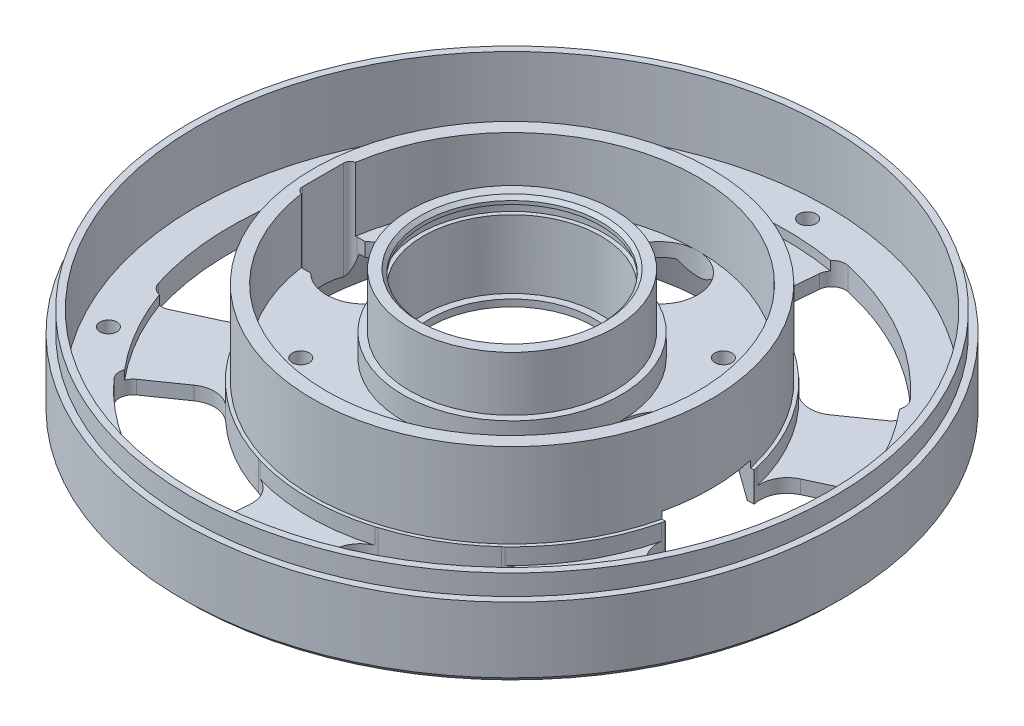
SolidWorks part; units mm, degrees
material "5052-H32"
ref_plane "Front Plane" through (0, 0, 0) normal (0, 0, 1) x (1, 0, 0)
ref_plane "Top Plane" through (0, 0, 0) normal (0, 1, 0) x (1, 0, 0)
ref_plane "Right Plane" through (0, 0, 0) normal (1, 0, 0) x (0, 0, -1)
ref_axis "Axis1" through (0, 0, 0) along (0, 1, 0)
sketch "Sketch1" plane through (0, 0, 0) normal (0, 0, 1) x (1, 0, 0)
  line L0 (0, 0) -> (0, -50000) construction
  line L1 (-13, 8.15) -> (-13, -4.15)
  line L2 (-13, -4.15) -> (-12, -4.15)
  line L4 (45.1, 8.15) -> (-45.1, 8.15) construction
  line L5 (-12.75, -4.15) -> (12.75, -4.15) construction
  line L7 (-13, 8.15) -> (-15, 8.15)
  line L8 (-15, 8.15) -> (-15, -3.15)
  line L9 (-15, -3.15) -> (-28.25, -3.15)
  line L10 (-12, -5.15) -> (-28.25, -5.15)
  line L12 (-28.25, -5.15) -> (-28.25, -3.15)
  line L13 (-29.25, 6) -> (-29.25, -6) construction
  line L16 (-12, -4.15) -> (-12, -5.15)
  dimension "D1" = 1
  dimension "D2" = 30
  dimension "D3" = 2
  dimension "D4" = 1
  dimension "D5" = 1
  dimension "D6" = 26
revolve "Revolve1" add sketch "Sketch1" angle 360 about L0
sketch "Sketch4" plane through (0, 0, 0) normal (0, 0, 1) x (1, 0, 0)
  line L1 (-29.75, -8.5) -> (-40.35, -8.5)
  line L2 (-46.35, -7.15) -> (-46.35, 3)
  line L3 (-46.35, 3) -> (-47.35, 3)
  line L4 (-47.35, 3) -> (-47.35, 0)
  line L5 (-47.35, 0) -> (-48.35, 0)
  line L6 (-48.35, 0) -> (-48.35, -9.6235)
  line L7 (-47.4735, -10.5) -> (-28.75, -10.5)
  line L8 (-28.75, -10.5) -> (-26.75, -5.15)
  line L9 (-29.75, -8.5) -> (-29.75, -6.1361)
  line L10 (-26.75, -5.15) -> (-26.75, -3.15)
  line L12 (-48.35, -9.6235) -> (-47.4735, -10.5)
  line L13 (-45.1, 8.15) -> (-45.1, -6.15) construction
  line L14 (-46.35, -7.15) -> (-40.35, -7.15)
  line L15 (-40.35, -7.15) -> (-40.35, -8.5)
  line L16 (-45.1, -6.15) -> (45.1, -6.15) construction
  line L18 (-44.85, -7.15) -> (-44.85, -10.5) construction
  line L20 (-41.85, -7.15) -> (-41.85, -10.5) construction
  line L22 (-29.75, -6.1361) -> (-29.23, -6.1361)
  line L24 (-29.23, -6.1361) -> (-29.23, -3.15)
  line L25 (-29.23, -3.15) -> (-26.75, -3.15)
  line L26 (28.25, -3.15) -> (-28.25, -3.15) construction
  line L27 (-39.5, -7.5) -> (39.5, -7.5) construction
  line L28 (0, 0) -> (0, 50000) construction
  line L29 (-30.25, -6) -> (-30.25, -7.5) construction
  line L33 (-28.25, -5.15) -> (28.25, -5.15) construction
  dimension "D1" = 2
  dimension "D2" = 3
  dimension "D3" = 1
  dimension "D4" = 2
  dimension "D5" = 0.5
  dimension "D6" = 1
  dimension "D7" = 1.25
  dimension "D8" = 135
  dimension "D9" = 3
  dimension "D10" = 1.5
  dimension "D11" = 1.5
  dimension "D12" = 2
  dimension "D13" = 1
  dimension "D14" = 58.46
revolve "Revolve2" add sketch "Sketch4" angle 360 about axis through (0, 0, 0) along (0, 1, 0)
sketch "Sketch6" plane through (0, 0, 0) normal (0, 0, 1) x (1, 0, 0)
  line L0 (-29.23, 6.233) -> (-27.23, 6.233)
  line L1 (-27.23, 6.233) -> (-27.23, -3.15)
  line L2 (-27.23, -3.15) -> (-29.23, -3.15)
  line L3 (-29.23, -3.15) -> (-29.23, 6.233)
  line L6 (29.23, -3.15) -> (-29.23, -3.15) construction
  dimension "D1" = 2
revolve "Revolve3" add sketch "Sketch6" angle 360 about axis through (0, 0, 0) along (0, 1, 0)
sketch "Sketch7" plane through (0, 0, 0) normal (0, 0, 1) x (1, 0, 0)
  line L0 (40.35, -8.5) -> (-40.35, -8.5) construction
  line L1 (-29.7176, -6.1376) -> (-29.23, -6.1376)
  line L2 (-29.73, -6.15) -> (-29.73, -8.5)
  line L3 (-29.73, -8.5) -> (-29.23, -8.5)
  line L4 (-29.23, -6.1376) -> (-29.23, -8.5)
  line L5 (-29.23, 6.233) -> (-29.23, -6.1361) construction
  line L6 (-29.7176, -6.1376) -> (-29.73, -6.15)
  line L7 (29.75, -8.5) -> (-29.75, -8.5) construction
  line L8 (-31.759, -6.15) -> (-25.7399, -6.15) construction
  dimension "D1" = 135
  dimension "D2" = 0.5
revolve "Revolve4" add sketch "Sketch7" angle 360 about axis through (0, 0, 0) along (0, 1, 0)
sketch "Sketch8" plane through (0, -5.15, 0) normal (0, -1, 0) x (1, 0, 0)
  circle A0 centre (-15.5, 15.5) radius 3.5
  circle A1 centre (15.5, 15.5) radius 3.5
  circle A2 centre (15.5, -15.5) radius 3.5
  circle A3 centre (-15.5, -15.5) radius 3.5
  dimension "D1" = 7
sketch "Sketch10" plane through (0, 0, 0) normal (0, 0, 1) x (1, 0, 0)
  line L0 (-15.25, 0.15) -> (15.25, 0.15) construction
  line L1 (-15, -3.15) -> (-16, -3.15)
  line L2 (-15, -3.15) -> (-15, 0.15)
  line L3 (-15, 0.15) -> (-16, 0.15)
  line L4 (-16, -3.15) -> (-16, 0.15)
  line L5 (-15, 8.15) -> (-15, -3.15) construction
  line L6 (15, -3.15) -> (-15, -3.15) construction
  dimension "D1" = 1
revolve "Revolve5" add sketch "Sketch10" angle 360 about axis through (0, 0, 0) along (0, 1, 0)
sketch "Sketch12" plane through (0, 0, 0) normal (0, 1, 0) x (1, 0, 0)
  circle A0 centre (-21.615, 0) radius 5.615
  circle A1 centre (0, 0) radius 16 construction
  circle A2 centre (0, 0) radius 27.23 construction
extrude "Cut-Extrude2" cut sketch "Sketch12" against normal through all
pattern_circular "CirPattern3" count 4 over 360 about axis through (0, 0, 0) along (0, 1, 0) skipping 1 of "Cut-Extrude2"
extrude "Boss-Extrude1" add sketch "Sketch8" along normal up to surface (3.85 mm away)
hole_wizard "M3x0.5 Tapped Hole1" positions "Sketch14" profile "Sketch15" tap size "M3x0.5" standard "ANSI Metric" end condition through all
sketch "Sketch14" plane through (0, -9, 0) normal (0, -1, 0) x (-1, 0, 0)
  point P0 (-15.5, 15.5)
  point P3 (15.5, 15.5)
  point P6 (15.5, -15.5)
  point P9 (-15.5, -15.5)
cosmetic thread "Hole Thread1" parameters "D2"=3
cosmetic thread "Hole Thread2" parameters "D2"=3
cosmetic thread "Hole Thread3" parameters "D2"=3
cosmetic thread "Hole Thread4" parameters "D2"=3
sketch "Sketch15" plane through (15.5, -9, -15.5) normal (1, 0, 0) x (0, 0, -1)
  line L0 (0, 0) -> (0, 17.15)
  line L1 (0, 17.15) -> (1.25, 17.15)
  line L2 (1.25, 17.15) -> (1.25, 0)
  line L5 (1.25, 0) -> (0, 0)
  line L11 (0, -6.35) -> (0, 107.95) construction
  dimension "Thru Tap Drill Dia." = 2.5
  dimension "Thru Tap Drill Depth" = 17.15
hole_wizard "M3x0.5 Tapped Hole3" positions "Sketch19" profile "Sketch20" tap size "M3x0.5" standard "ANSI Metric" end condition through all
sketch "Sketch19" plane through (0, -10.5, 0) normal (0, -1, 0) x (-1, 0, 0)
  line L0 (0, 0) -> (0, 43.35) construction
  line L3 (0, 0) -> (-50000, 0) construction
  circle A1 centre (0, 0) radius 43.35 construction
  circle A2 centre (0, 0) radius 40.35 construction
  point P0 (0, 43.35)
  dimension "D1" = 3
  dimension "D2" = 90
sketch "Sketch20" plane through (0, -10.5, -43.35) normal (1, 0, 0) x (0, 0, -1)
  line L0 (0, 0) -> (0, 18.65)
  line L1 (0, 18.65) -> (1.25, 18.65)
  line L2 (1.25, 18.65) -> (1.25, 0.5)
  line L3 (1.25, 0.5) -> (1.75, 0)
  line L5 (1.75, 0) -> (0, 0)
  line L6 (-1.25, 0.5) -> (-1.75, 0) construction
  line L11 (0, -6.35) -> (0, 107.95) construction
  dimension "Thru Tap Drill Dia." = 2.5
  dimension "Thru Tap Drill Depth" = 18.65
  dimension "Near C'Sink Dia." = 3.5
  dimension "Near C'Sink Angle" = 90
cosmetic thread "Hole Thread7" parameters "D2"=3
pattern_circular "CirPattern4" count 6 over 360 about axis through (0, 0, 0) along (0, 1, 0) of "M3x0.5 Tapped Hole3"
sketch "Sketch24" plane through (0, -10.5, 0) normal (0, -1, 0) x (1, 0, 0)
  line L9 (-25.6489, 5.5) -> (-44.2117, 5.5)
  line L10 (-25.6489, 5.5) -> (-25.6489, -5.5)
  line L11 (-25.6489, -5.5) -> (-44.2117, -5.5)
  line L12 (-46.2117, 3.5) -> (-46.2117, -3.5)
  arc A5 (-44.2117, -5.5) -> (-46.2117, -3.5) centre (-44.2117, -3.5) cw
  arc A6 (-44.2117, 5.5) -> (-46.2117, 3.5) centre (-44.2117, 3.5) ccw
  circle A7 centre (0, 0) radius 46.35 construction
  point P5 (-25.6489, 0)
  dimension "D2" = 2
  dimension "D1" = 11
extrude "Cut-Extrude6" [suppressed] cut sketch "Sketch24" against normal up to surface (1.5 mm away)
sketch "Sketch25" plane through (0, -10.5, 0) normal (0, -1, 0) x (1, 0, 0)
  line L5 (-25.6489, 5.5) -> (-44.2117, 5.5) construction
  line L9 (-34.6807, 5.5) -> (-44.2117, 5.5)
  line L10 (-34.6807, 5.5) -> (-34.6807, -5.5)
  line L11 (-34.6807, -5.5) -> (-44.2117, -5.5)
  line L12 (-46.2117, 3.5) -> (-46.2117, -3.5)
  line L13 (-25.6489, -5.5) -> (-44.2117, -5.5) construction
  line L14 (-46.2117, 3.5) -> (-46.2117, -3.5) construction
  arc A3 (-44.2117, -5.5) -> (-46.2117, -3.5) centre (-44.2117, -3.5) cw
  arc A4 (-44.2117, 5.5) -> (-46.2117, 3.5) centre (-44.2117, 3.5) ccw
  point P12 (-46.2117, -5.5)
  dimension "D1" = 2
extrude "Cut-Extrude7" [suppressed] cut sketch "Sketch25" against normal through all
sketch "Sketch26" plane through (0, 0, 0) normal (0, 1, 0) x (1, 0, 0)
  line L0 (0, 0) -> (-50000, 0) construction
  line L1 (31.1951, 11.1252) -> (36.6728, 13.6795)
  line L2 (31.1951, -11.1252) -> (36.6728, -13.6795)
  arc A0 (39.4249, 12.47) -> (39.4249, -12.47) centre (0, 0) cw
  arc A1 (28.9857, 6.6106) -> (28.9857, -6.6106) centre (0, 0) cw
  arc A2 (28.9857, -6.6106) -> (31.1951, -11.1252) centre (32.8856, -7.5) ccw
  arc A3 (28.9857, 6.6106) -> (31.1951, 11.1252) centre (32.8856, 7.5) cw
  circle A4 centre (0, 0) radius 46.35 construction
  arc A6 (39.4249, -12.47) -> (36.6728, -13.6795) centre (37.518, -11.8669) cw
  arc A7 (39.4249, 12.47) -> (36.6728, 13.6795) centre (37.518, 11.8669) ccw
  circle A8 centre (0, 0) radius 29.23 construction
  point P12 (28.108, -9.6857)
  point P15 (28.108, 9.6857)
  point P20 (38.6807, -14.6158)
  point P26 (38.6807, 14.6158)
  dimension "D1" = 4
  dimension "D2" = 0.5
  dimension "D4" = 2
  dimension "D6" = 5
  dimension "D3" = 50
  dimension "D5" = 15
extrude "Cut-Extrude8" cut sketch "Sketch26" against normal through all both and the other way through all
pattern_circular "CirPattern5" count 6 over 360 about axis through (0, 0, 0) along (0, 1, 0) of "Cut-Extrude8"
sketch "Sketch30" plane through (0, -10.5, 0) normal (0, -1, 0) x (1, 0, 0)
  line L1 (6.6135, 5) -> (34.3769, 5)
  line L2 (6.6135, 5) -> (6.6135, -5)
  line L3 (6.6135, -5) -> (34.3769, -5)
  line L4 (34.3769, 5) -> (34.3769, -5)
  point P4 (6.6135, 0)
  dimension "D1" = 10
extrude "Cut-Extrude13" [suppressed] cut sketch "Sketch30" against normal up to surface (5.35 mm away) up to face at (-15.5, -5.15, -19)
sketch "Sketch31" plane through (0, 0, 0) normal (0, 0, 1) x (1, 0, 0)
  line L0 (0, 0) -> (0, -50000) construction
  line L1 (13, 8.15) -> (-13, 8.15) construction
  line L2 (-5.4339, 7.15) -> (-13.6, 7.15)
  line L3 (-5.4339, 7.15) -> (-5.4339, 5.85)
  line L4 (-5.4339, 5.85) -> (-13.6, 5.85)
  line L5 (-13.6, 7.15) -> (-13.6, 5.85)
  dimension "D1" = 1.3
  dimension "D2" = 1
  dimension "D3" = 27.2
revolve "Cut-Revolve1" cut sketch "Sketch31" angle 360 about L0
chamfer "Chamfer1" distance 0.5 angle 45 1 edges at (0, 8.15, 13)
sketch "Sketch32" plane through (0, 0, 0) normal (0, 1, 0) x (1, 0, 0)
  line L1 (-18.73, 4) -> (-26.73, 4)
  line L2 (-17.73, 3) -> (-17.73, -3)
  line L3 (-18.73, -4) -> (-26.73, -4)
  line L4 (-27.73, 3) -> (-27.73, -3)
  arc A0 (-26.73, 4) -> (-27.73, 3) centre (-26.73, 3) ccw
  arc A1 (-17.73, -3) -> (-18.73, -4) centre (-18.73, -3) cw
  arc A2 (-26.73, -4) -> (-27.73, -3) centre (-26.73, -3) cw
  arc A3 (-18.73, 4) -> (-17.73, 3) centre (-18.73, 3) cw
  circle A4 centre (0, 0) radius 27.23 construction
  circle A5 centre (0, 0) radius 27.23 construction
  point P4 (-17.73, 0)
  point P16 (-27.23, 0)
  dimension "D2" = 1
  dimension "D3" = 0.5
  dimension "D1" = 8
  dimension "D4" = 10
extrude "Cut-Extrude14" cut sketch "Sketch32" against normal through all both and the other way through all
sketch "Sketch33" plane through (0, 0, 0) normal (0, 1, 0) x (1, 0, 0)
  line L1 (33.3439, -6.5) -> (25.7584, -6.5)
  line L2 (33.3439, -6.5) -> (33.3439, 6.5)
  line L3 (33.3439, 6.5) -> (25.7584, 6.5)
  line L4 (25.7584, -6.5) -> (25.7584, 6.5)
  line L5 (33.3439, -6.5) -> (25.7584, 6.5) construction
  line L6 (33.3439, 6.5) -> (25.7584, -6.5) construction
  point P0 (29.5512, 0)
  dimension "D1" = 13
extrude "Cut-Extrude15" cut sketch "Sketch33" along normal up to surface (-5.15 mm away) from offset 20 up to face at (-6.341, -5.15, -3.4511) offset against normal yes
pattern_circular "CirPattern6" [suppressed] count 6 over 360 about axis through (0, 0, 0) along (0, 1, 0) of bodies 145
sketch "Sketch34" plane through (0, -5.15, 0) normal (0, -1, 0) x (1, 0, 0)
  line L0 (4.7, 19) -> (-2.3, 12) construction
  line L1 (-1.8, 19) -> (4.2, 19)
  line L2 (-2.3, 18.5) -> (-2.3, 12.5)
  line L3 (-1.8, 12) -> (4.2, 12)
  line L4 (4.7, 18.5) -> (4.7, 12.5)
  arc A0 (4.2, 19) -> (4.7, 18.5) centre (4.2, 18.5) cw
  arc A1 (-2.3, 12.5) -> (-1.8, 12) centre (-1.8, 12.5) ccw
  arc A2 (4.2, 12) -> (4.7, 12.5) centre (4.2, 12.5) ccw
  arc A3 (-1.8, 19) -> (-2.3, 18.5) centre (-1.8, 18.5) ccw
  point P4 (1.2, 15.5)
  point P5 (2.4824, -15.5)
  dimension "D5" = 0.5
  dimension "D1" = 7
  dimension "D2" = 7
  dimension "D3" = 15.5
  dimension "D4" = 1.2
extrude "Boss-Extrude2" add sketch "Sketch34" along normal offset from surface (2.35 mm away) 1.5
